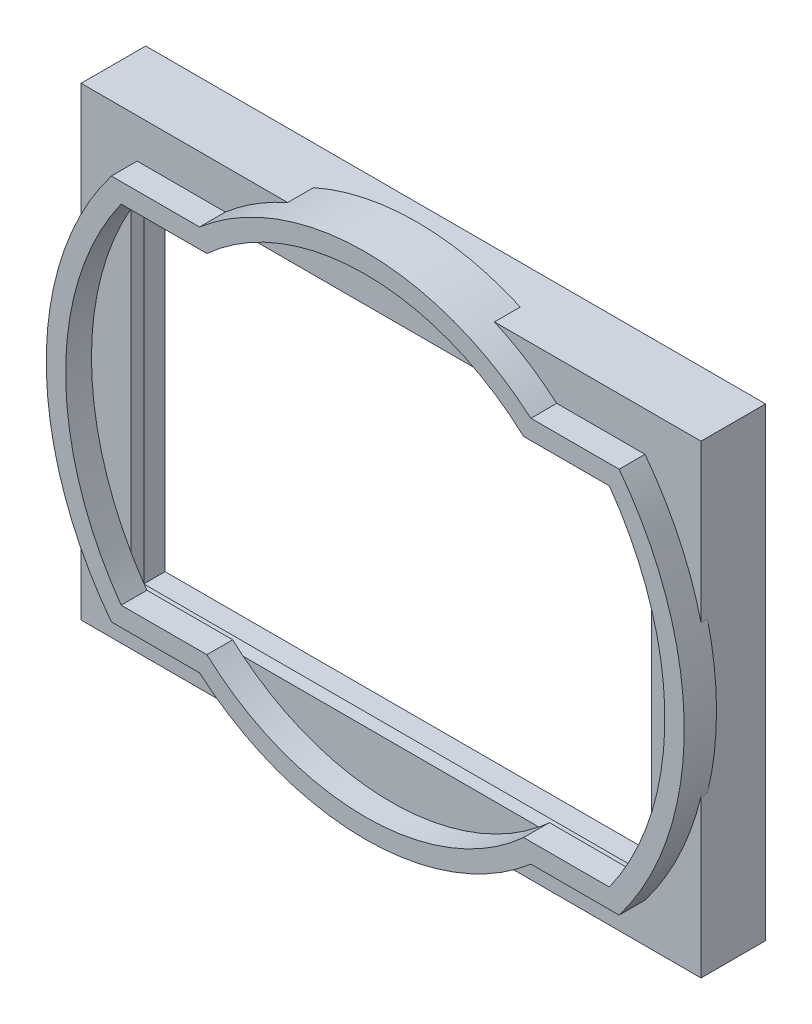
SolidWorks part; units mm, degrees
ref_plane "前视基准面" through (0, 0, 0) normal (0, 0, 1) x (1, 0, 0)
ref_plane "上视基准面" through (0, 0, 0) normal (0, 1, 0) x (1, 0, 0)
ref_plane "右视基准面" through (0, 0, 0) normal (1, 0, 0) x (0, 0, -1)
other "Configuration Table"
sketch "草图1" plane through (0, 0, 0) normal (0, 0, 1) x (1, 0, 0)
  line L0 (-18.9034, 13.45) -> (-12.2612, 13.45)
  line L1 (18.9034, 13.45) -> (-18.9034, -13.45) construction
  line L2 (-18.9034, -13.45) -> (-12.2612, -13.45)
  line L3 (12.2612, 13.45) -> (18.9034, 13.45)
  line L4 (12.2612, -13.45) -> (18.9034, -13.45)
  line L5 (-19.6618, 14.95) -> (-12.8292, 14.95)
  line L6 (12.8292, 14.95) -> (19.6618, 14.95)
  line L7 (12.8292, -14.95) -> (19.6618, -14.95)
  line L8 (-19.6618, -14.95) -> (-12.8292, -14.95)
  arc A0 (-18.9034, 13.45) -> (-18.9034, -13.45) centre (0, 0) ccw
  arc A1 (-12.2612, -13.45) -> (12.2612, -13.45) centre (0, 0) ccw
  arc A2 (12.2612, 13.45) -> (-12.2612, 13.45) centre (0, 0) ccw
  arc A3 (18.9034, -13.45) -> (18.9034, 13.45) centre (0, 0) ccw
  arc A4 (12.8292, 14.95) -> (-12.8292, 14.95) centre (0, 0) ccw
  arc A5 (19.6618, -14.95) -> (19.6618, 14.95) centre (0, 0) ccw
  arc A6 (-12.8292, -14.95) -> (12.8292, -14.95) centre (0, 0) ccw
  arc A7 (-19.6618, 14.95) -> (-19.6618, -14.95) centre (0, 0) ccw
  dimension "D1" = 36.4
  dimension "D2" = 46.4
  dimension "D3" = 26.9
  dimension "D4" = 1.5
extrude "凸台-拉伸1" add sketch "草图1" along normal blind 2
sketch "草图3" plane through (0, 0, 0) normal (0, 0, -1) x (-1, 0, 0)
  line L1 (-21.5, -15.5) -> (21.5, -15.5)
  line L2 (-21.5, -15.5) -> (-21.5, 15.5)
  line L3 (-21.5, 15.5) -> (21.5, 15.5)
  line L4 (21.5, -15.5) -> (21.5, 15.5)
  line L5 (-21.5, -15.5) -> (21.5, 15.5) construction
  line L6 (-21.5, 15.5) -> (21.5, -15.5) construction
  line L7 (-20.15, -14.15) -> (20.15, -14.15)
  line L8 (-20.15, -14.15) -> (-20.15, 14.15)
  line L9 (-20.15, 14.15) -> (20.15, 14.15)
  line L10 (20.15, -14.15) -> (20.15, 14.15)
  line L11 (-20.15, -14.15) -> (20.15, 14.15) construction
  line L12 (-20.15, 14.15) -> (20.15, -14.15) construction
  point P0 (0, 0)
  point P6 (0, 0)
  arc M3 (19.6618, -14.95) -> (19.6618, 14.95) centre (0, 0) ccw
  line M4 (19.6618, 14.95) -> (12.8292, 14.95)
  arc M5 (12.8292, 14.95) -> (-12.8292, 14.95) centre (0, 0) ccw
  line M6 (-12.8292, 14.95) -> (-19.6618, 14.95)
  arc M7 (-19.6618, 14.95) -> (-19.6618, -14.95) centre (0, 0) ccw
  line M8 (-19.6618, -14.95) -> (-12.8292, -14.95)
  arc M9 (-12.8292, -14.95) -> (12.8292, -14.95) centre (0, 0) ccw
  line M10 (12.8292, -14.95) -> (19.6618, -14.95)
  arc M11 (-12.2612, 13.45) -> (12.2612, 13.45) centre (0, 0) cw
  arc M13 (18.9034, 13.45) -> (18.9034, -13.45) centre (0, 0) cw
  arc M15 (12.2612, -13.45) -> (-12.2612, -13.45) centre (0, 0) cw
  arc M17 (-18.9034, -13.45) -> (-18.9034, 13.45) centre (0, 0) cw
  dimension "D1" = 43
  dimension "D2" = 31
  dimension "D3" = 40.3
  dimension "D4" = 28.3
extrude "凸台-拉伸2" add sketch "草图3" along normal blind 2 contours L3 L2 M7 M6 M5 | L8 L9 L3 L2 M11 M5 M6 M7 M17 | L9 L3 M11 | L3 M11 | L3 M5 M11 | L10 L4 L3 L9 M13 M3 M4 M5 M11 | L4 L3 M3 M5 M4 | L10 L4 M13 | L4 M3 M13 | L4 M13 | L10 L7 L1 L4 M15 M9 M10 M3 M13 | L1 L4 M3 M10 M9 | L7 L1 M15 | L1 M9 M15 | L1 M15 | L7 L8 L2 L1 M17 M7 M8 M9 M15 | L2 L1 M9 M8 M7 | L2 M7 M17 | L8 L2 M17 | L2 M17 region at (21.4008, -13.8295, 0) region at (12.4099, -15.1224, 0) region at (10.8489, -15.7468, 0) region at (24.4547, 0, 0) region at (0, -14.8047, 0) region at (0, -16.5872, 0) region at (-12.56, -15.3054, 0) region at (-10.8489, -15.3625, 0) region at (22.1822, 0, 0) region at (20.7944, 0, 0) region at (20.5133, 13.51, 0) region at (21.4008, 13.8295, 0) region at (-21.7453, -10.4381, 0) region at (0, 19.4532, 0) region at (-20.7944, 0, 0) region at (-22.1822, 0, 0) region at (-20.711, 13.6402, 0) region at (-21.3625, 10.4381, 0) region at (0, 16.5872, 0) region at (0, 14.8047, 0)
sketch "草图4" plane through (0, 0, -2) normal (0, 0, -1) x (-1, 0, 0)
  line L1 (-22.5, -16.5) -> (22.5, -16.5)
  line L2 (-22.5, -16.5) -> (-22.5, 16.5)
  line L3 (-22.5, 16.5) -> (22.5, 16.5)
  line L4 (22.5, -16.5) -> (22.5, 16.5)
  line L5 (-22.5, -16.5) -> (22.5, 16.5) construction
  line L6 (-22.5, 16.5) -> (22.5, -16.5) construction
  line L7 (-24, -18) -> (24, -18)
  line L8 (-24, -18) -> (-24, 18)
  line L9 (-24, 18) -> (24, 18)
  line L10 (24, -18) -> (24, 18)
  line L11 (-24, -18) -> (24, 18) construction
  line L12 (-24, 18) -> (24, -18) construction
  point P0 (0, 0)
  point P6 (0, 0)
  arc M6 (-12.1589, -15.5) -> (12.1589, -15.5) centre (0, 0) ccw
  line M7 (12.1589, -15.5) -> (21.5, -15.5)
  line M8 (21.5, -15.5) -> (21.5, -12.1589)
  arc M9 (21.5, -12.1589) -> (21.5, 12.1589) centre (0, 0) ccw
  line M10 (21.5, 12.1589) -> (21.5, 15.5)
  line M11 (21.5, 15.5) -> (12.1589, 15.5)
  arc M12 (12.1589, 15.5) -> (-12.1589, 15.5) centre (0, 0) ccw
  line M13 (-12.1589, 15.5) -> (-21.5, 15.5)
  line M14 (-21.5, 15.5) -> (-21.5, 12.1589)
  arc M15 (-21.5, 12.1589) -> (-21.5, -12.1589) centre (0, 0) ccw
  line M16 (-21.5, -12.1589) -> (-21.5, -15.5)
  line M17 (-21.5, -15.5) -> (-12.1589, -15.5)
  dimension "D1" = 45
  dimension "D2" = 33
  dimension "D3" = 48
  dimension "D4" = 36
extrude "凸台-拉伸3" add sketch "草图4" along normal blind 3
extrude "凸台-拉伸4" add sketch "草图4<2>" against normal blind 2 contours L10 L9 L3 L4 M9 M12 | L4 L3 M9 M12 M11 M10 | L9 L8 L2 L3 M15 M12 | L3 L2 M15 M14 M13 M12 | L2 L1 M6 M17 M16 M15 | L8 L7 L1 L2 M6 M15 | L1 L4 M9 M8 M7 M6 | L7 L10 L4 L1 M9 M6 region at (22.3667, -13.3451, -2) region at (16.6314, -16.7009, -2) region at (-11.5494, -16.1236, -2) region at (-16.6314, -16.7009, -2) region at (23.5415, 8.1149, -2) region at (22.3667, 13.3451, -2) region at (-22.1408, 11.2461, -2) region at (-22.7009, 13.3451, -2)
sketch "草图4<2>" plane through (0, 0, -2) normal (0, 0, -1) x (-1, 0, 0) same geometry as "草图4"
extrude "切除-拉伸1" cut sketch "草图4<3>" against normal blind 1.5 contours L8 M15 | L10 M9 region at (24.2803, 0, -2) region at (-24.2803, 0, -2)
sketch "草图4<3>" plane through (0, 0, -2) normal (0, 0, -1) x (-1, 0, 0) same geometry as "草图4"
sketch "草图5" plane through (0, 0, -2) normal (0, 0, -1) x (-1, 0, 0)
  line L1 (-21.15, -15.15) -> (21.15, -15.15)
  line L2 (-21.15, -15.15) -> (-21.15, 15.15)
  line L3 (-21.15, 15.15) -> (21.15, 15.15)
  line L4 (21.15, -15.15) -> (21.15, 15.15)
  line L5 (-21.15, -15.15) -> (21.15, 15.15) construction
  line L6 (-21.15, 15.15) -> (21.15, -15.15) construction
  point P0 (0, 0)
  dimension "D1" = 42.3
  dimension "D2" = 30.3
extrude "切除-拉伸2" cut sketch "草图5" against normal blind 1
